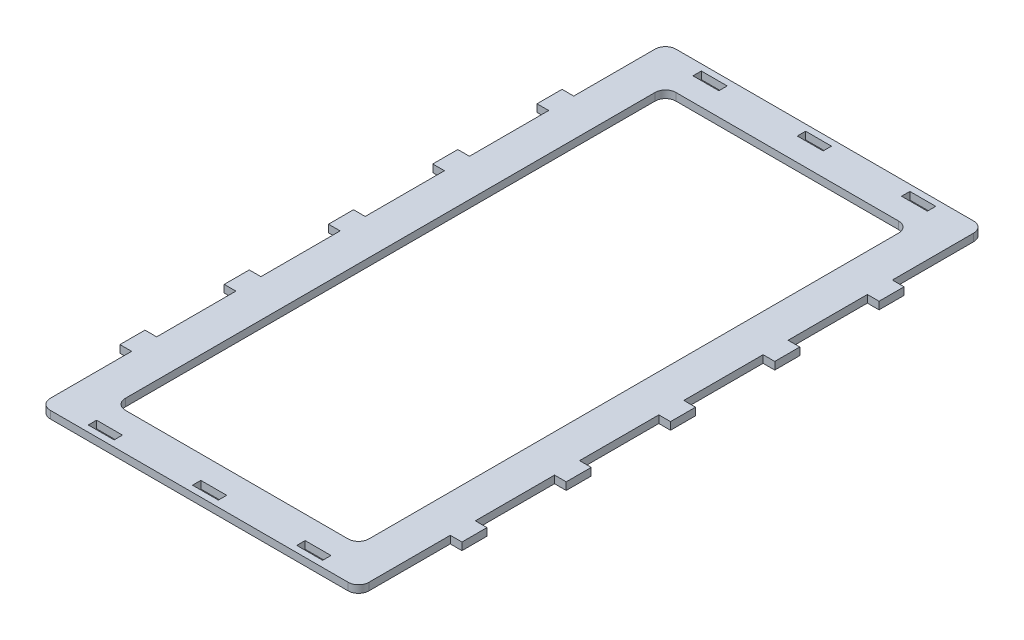
SolidWorks part; units mm, degrees
ref_plane "前视基准面" through (0, 0, 0) normal (0, 0, 1) x (1, 0, 0)
ref_plane "上视基准面" through (0, 0, 0) normal (0, 1, 0) x (1, 0, 0)
ref_plane "右视基准面" through (0, 0, 0) normal (1, 0, 0) x (0, 0, -1)
other "Configuration Table"
sketch "草图1" plane through (0, 0, 0) normal (0, 1, 0) x (1, 0, 0)
  line L1 (-382, 750) -> (382, 750)
  line L2 (-382, 750) -> (-382, -750)
  line L3 (-382, -750) -> (382, -750)
  line L4 (382, 750) -> (382, -750)
  line L5 (-410, -470) -> (-382, -470)
  line L6 (-410, -470) -> (-410, -530)
  line L7 (-410, -530) -> (-382, -530)
  line L8 (-382, -470) -> (-382, -530)
  line L9 (-281, -735) -> (-219, -735)
  line L10 (-281, -735) -> (-281, -715)
  line L11 (-281, -715) -> (-219, -715)
  line L12 (-219, -735) -> (-219, -715)
  line L13 (-292, 660) -> (292, 660)
  line L14 (-292, 660) -> (-292, -660)
  line L15 (-292, -660) -> (292, -660)
  line L16 (292, 660) -> (292, -660)
  point P4 (-382, 0)
  point P6 (0, -750)
  point P11 (-410, -500)
  point P20 (0, -660)
  point P21 (-292, 0)
  point P22 (-250, -735)
  point P23 (-219, -725)
  dimension "D1" = 764
  dimension "D2" = 1500
  dimension "D3" = 250
  dimension "D4" = 28
  dimension "D5" = 60
  dimension "D6" = 90
  dimension "D7" = 90
  dimension "D8" = 62
  dimension "D9" = 20
  dimension "D10" = 132
  dimension "D11" = 25
extrude "凸台-拉伸1" add sketch "草图1" along normal blind 18 contours L2 L3 L4 L1 | L14 L15 L16 L13
extrude "凸台-拉伸2" add sketch "草图1<3>" along normal up to surface (18 mm away) contours L6 L7 L8 L5 up to face at (0, 18, 0)
sketch "草图1<3>" plane through (0, 0, 0) normal (0, 1, 0) x (1, 0, 0) same geometry as "草图1"
pattern_linear "阵列(线性)1" count 5 spacing 250 along (0, 0, -1) of "凸台-拉伸2"
mirror "镜向1" about plane through (0, 0, 0) normal (1, 0, 0) of "阵列(线性)1", "凸台-拉伸2"
extrude "切除-拉伸1" cut sketch "草图1<4>" along normal through all contours L12 L11 L10 L9
sketch "草图1<4>" plane through (0, 0, 0) normal (0, 1, 0) x (1, 0, 0) same geometry as "草图1"
pattern_linear "阵列(线性)2" count 3 spacing 250 along (1, 0, 0) of "切除-拉伸1"
mirror "镜向2" about plane through (0, 0, 0) normal (0, 0, 1) of "阵列(线性)2", "切除-拉伸1"
fillet "圆角1" radius 25 4 edges at (-382, 9, -750) (382, 9, -750) (382, 9, 750) (-382, 9, 750)
fillet "圆角2" radius 25 4 edges at (-292, 9, -660) (292, 9, -660) (292, 9, 660) (-292, 9, 660)
